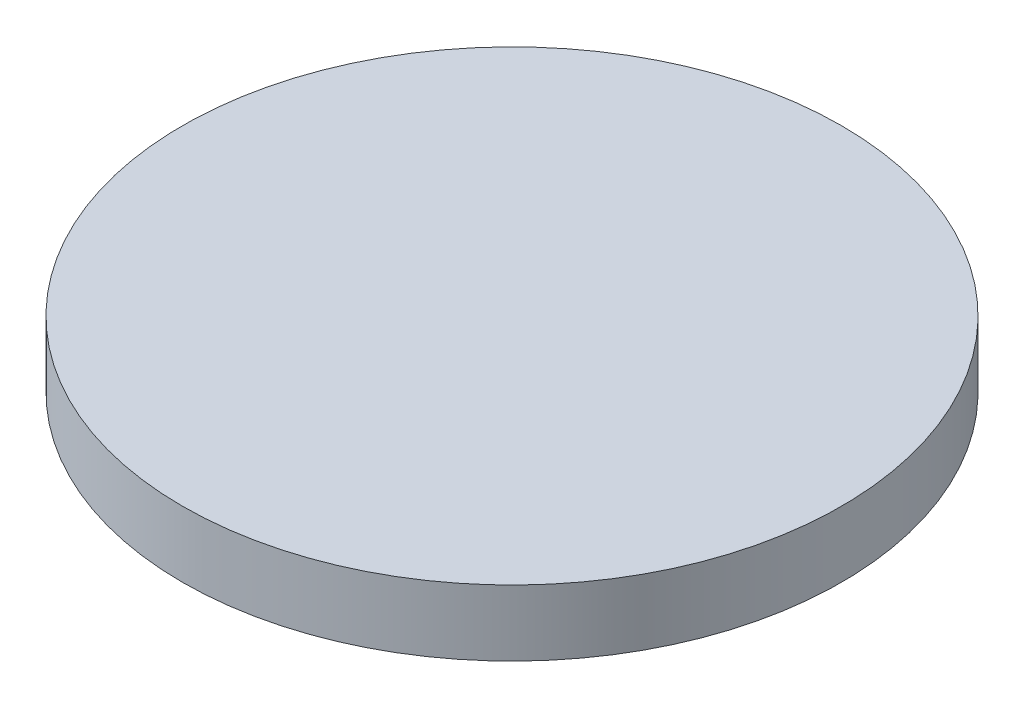
SolidWorks part; units mm, degrees
ref_plane "Front Plane" through (0, 0, 0) normal (0, 0, 1) x (1, 0, 0)
ref_plane "Top Plane" through (0, 0, 0) normal (0, 1, 0) x (1, 0, 0)
ref_plane "Right Plane" through (0, 0, 0) normal (1, 0, 0) x (0, 0, -1)
sketch "Sketch1" plane through (0, 0, 0) normal (0, 1, 0) x (1, 0, 0)
  circle A0 centre (0, 0) radius 50
  dimension "D1" = 100
extrude "Boss-Extrude1" add sketch "Sketch1" along normal blind 10
